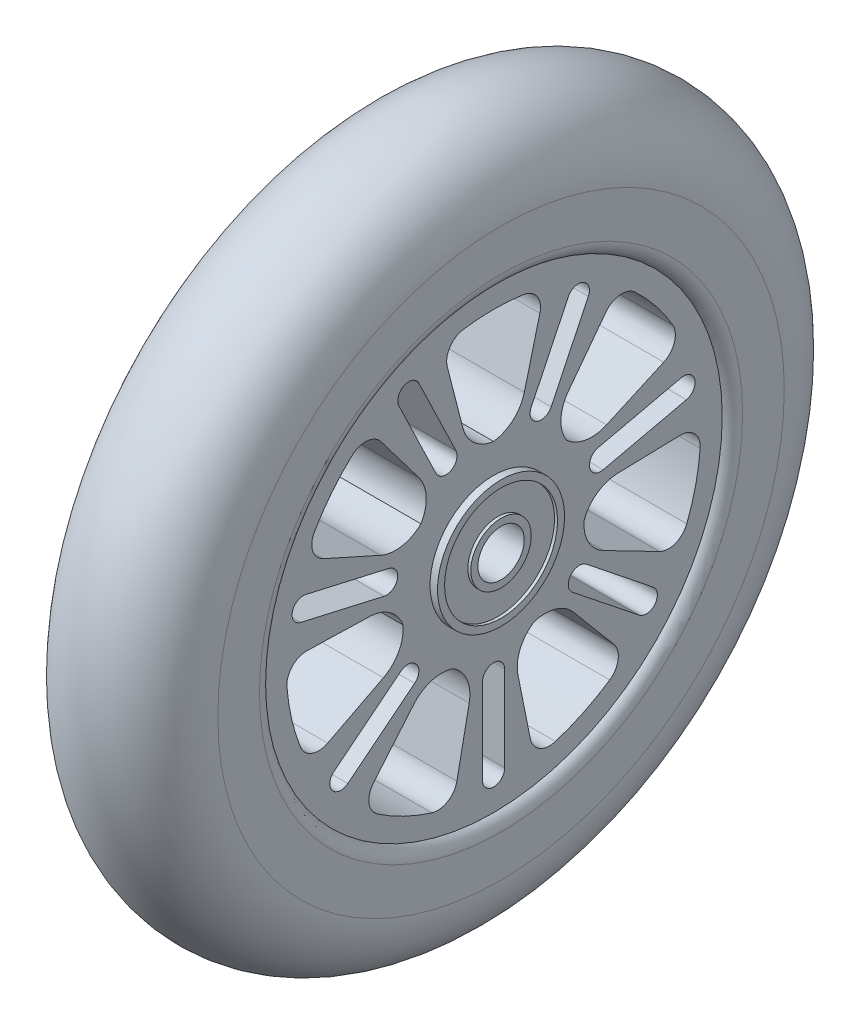
SolidWorks part; units mm, degrees
ref_plane "Front Plane" through (0, 0, 0) normal (0, 0, 1) x (1, 0, 0)
ref_plane "Top Plane" through (0, 0, 0) normal (0, 1, 0) x (1, 0, 0)
ref_plane "Right Plane" through (0, 0, 0) normal (1, 0, 0) x (0, 0, -1)
sketch "Sketch1" plane through (0, 0, 0) normal (0, 1, 0) x (1, 0, 0)
  line L0 (-12.065, 60.198) -> (-12.065, 0) construction
  line L1 (0, 0) -> (-24.13, 0)
  line L2 (0, 0) -> (0, 48.133)
  line L4 (-24.13, 0) -> (-24.13, 48.133)
  arc A0 (0, 48.133) -> (-24.13, 48.133) centre (-12.065, 48.133) ccw
  dimension "D1" = 60.198
  dimension "D2" = 24.13
revolve "Revolve1" add sketch "Sketch1" angle 360 about L1
sketch "Sketch2" plane through (0, 0, 0) normal (1, 0, 0) x (0, 0, -1)
  circle A0 centre (0, 0) radius 39.37 construction
  circle A1 centre (0, 0) radius 10.795 construction
  circle A2 centre (0, 0) radius 3.937
  dimension "D1" = 78.74
  dimension "D2" = 21.59
  dimension "D3" = 7.874
extrude "Cut-Extrude1" cut sketch "Sketch2" against normal through all
sketch "Sketch3" plane through (0, 0, 0) normal (1, 0, 0) x (0, 0, -1)
  line L0 (0.0012, -0.001) -> (-6.8326, 14.1885) construction
  line L1 (7.8687, 30.719) -> (5.2261, 20.4024)
  line L2 (-7.8687, 30.719) -> (-5.2261, 20.4024)
  line L3 (19.1114, 25.3058) -> (12.6932, 16.8074)
  line L4 (28.9235, 13.0018) -> (19.21, 8.6355)
  line L5 (31.701, 0.8368) -> (21.055, 0.5561)
  line L6 (28.1991, -14.5061) -> (18.7291, -9.634)
  line L7 (20.4198, -24.2623) -> (13.5627, -16.1139)
  line L8 (6.2409, -31.0905) -> (4.1456, -20.649)
  line L9 (-6.2371, -31.0914) -> (-4.1418, -20.6498)
  line L10 (-20.416, -24.2632) -> (-13.5589, -16.1148)
  line L11 (-28.1967, -14.508) -> (-18.7267, -9.636)
  line L12 (-31.6986, 0.8348) -> (-21.0525, 0.5541)
  line L13 (-28.9228, 13.0002) -> (-19.2092, 8.634)
  line L14 (-19.1107, 25.3042) -> (-12.6924, 16.8058)
  line L15 (-12.6962, 30.715) -> (-6.3919, 17.6251)
  line L16 (-16.0986, 29.0763) -> (-9.7944, 15.9865)
  line L17 (-17.3581, 36.043) -> (-23.3474, 48.4789) construction
  line L18 (-8.4846, 13.2669) -> (-8.4845, 13.2668)
  line L19 (16.0984, 29.0776) -> (9.7949, 15.9873)
  line L20 (12.6958, 30.716) -> (6.3924, 17.6257)
  line L21 (32.7713, 5.5441) -> (18.6068, 2.3107)
  line L22 (31.9308, 9.2259) -> (17.7663, 5.9924)
  line L23 (24.7675, -22.1641) -> (13.4081, -13.1059)
  line L24 (27.122, -19.2115) -> (15.7626, -10.1533)
  line L25 (-1.8859, -33.1824) -> (-1.8864, -18.6535)
  line L26 (1.8905, -33.1822) -> (1.89, -18.6534)
  line L27 (-27.1185, -19.2136) -> (-15.7597, -10.1546)
  line L28 (-24.7638, -22.1661) -> (-13.405, -13.1071)
  line L29 (-31.9295, 9.2234) -> (-17.7648, 5.9909)
  line L30 (-32.7697, 5.5416) -> (-18.605, 2.3091)
  circle A0 centre (0, 0) radius 40.005
  circle A1 centre (0, 0) radius 15.748
  arc A2 (5.1212, 34.8487) -> (-5.1212, 34.8487) centre (0, 0) ccw
  arc A3 (7.8687, 30.719) -> (5.1212, 34.8487) centre (4.636, 31.5471) ccw
  arc A4 (0, 15.7842) -> (5.2261, 20.4024) centre (-0.789, 21.9431) ccw
  arc A5 (0, 15.7842) -> (-5.2261, 20.4024) centre (0.789, 21.9431) cw
  arc A6 (-7.8687, 30.719) -> (-5.1212, 34.8487) centre (-4.636, 31.5471) cw
  arc A7 (19.1114, 25.3058) -> (24.0531, 25.7325) centre (21.7744, 23.2946) cw
  arc A8 (30.4392, 17.7247) -> (24.0531, 25.7325) centre (0.0004, 0.0008) ccw
  arc A9 (28.9235, 13.0018) -> (30.4392, 17.7247) centre (27.5554, 16.0455) ccw
  arc A10 (12.3409, 9.842) -> (19.21, 8.6355) centre (16.6643, 14.299) ccw
  arc A11 (12.3409, 9.842) -> (12.6932, 16.8074) centre (17.6482, 13.0652) cw
  arc A12 (31.701, 0.8368) -> (35.1157, -2.7608) centre (31.789, -2.4991) cw
  arc A13 (32.8366, -12.7464) -> (35.1157, -2.7608) centre (0.0012, 0.001) ccw
  arc A14 (28.1991, -14.5061) -> (32.8366, -12.7464) centre (29.7257, -11.5387) ccw
  arc A15 (15.3896, -3.5113) -> (18.7291, -9.634) centre (21.5698, -4.1126) ccw
  arc A16 (15.3896, -3.5113) -> (21.055, 0.5561) centre (21.2186, -5.6511) cw
  arc A17 (20.4198, -24.2623) -> (19.7362, -29.1751) centre (17.8666, -26.411) cw
  arc A18 (10.5081, -33.6191) -> (19.7362, -29.1751) centre (0.0019, 0.0004) ccw
  arc A19 (6.2409, -31.0905) -> (10.5081, -33.6191) centre (9.5128, -30.434) ccw
  arc A20 (6.8504, -14.2206) -> (4.1456, -20.649) centre (10.2336, -19.4273) ccw
  arc A21 (6.8504, -14.2206) -> (13.5627, -16.1139) centre (8.8118, -20.112) cw
  arc A22 (-6.2371, -31.0914) -> (-10.5043, -33.62) centre (-9.509, -30.4349) cw
  arc A23 (-19.7324, -29.176) -> (-10.5043, -33.62) centre (0.0019, -0.0004) ccw
  arc A24 (-20.416, -24.2632) -> (-19.7324, -29.176) centre (-17.8628, -26.4119) ccw
  arc A25 (-6.8466, -14.2215) -> (-13.5589, -16.1148) centre (-8.808, -20.1129) ccw
  arc A26 (-6.8466, -14.2215) -> (-4.1418, -20.6498) centre (-10.2298, -19.4282) cw
  arc A27 (-28.1967, -14.508) -> (-32.8341, -12.7483) centre (-29.7233, -11.5406) cw
  arc A28 (-35.1133, -2.7627) -> (-32.8341, -12.7483) centre (0.0012, -0.001) ccw
  arc A29 (-31.6986, 0.8348) -> (-35.1133, -2.7627) centre (-31.7865, -2.5011) ccw
  arc A30 (-15.3872, -3.5133) -> (-21.0525, 0.5541) centre (-21.2162, -5.653) ccw
  arc A31 (-15.3872, -3.5133) -> (-18.7267, -9.636) centre (-21.5673, -4.1145) cw
  arc A32 (-28.9228, 13.0002) -> (-30.4384, 17.7231) centre (-27.5546, 16.0439) cw
  arc A33 (-24.0524, 25.7309) -> (-30.4384, 17.7231) centre (0.0004, -0.0008) ccw
  arc A34 (-19.1107, 25.3042) -> (-24.0524, 25.7309) centre (-21.7736, 23.2931) ccw
  arc A35 (-12.3402, 9.8405) -> (-12.6924, 16.8058) centre (-17.6474, 13.0636) ccw
  arc A36 (-12.3402, 9.8405) -> (-19.2092, 8.634) centre (-16.6635, 14.2974) cw
  arc A37 (-12.6962, 30.715) -> (-16.0986, 29.0763) centre (-14.3974, 29.8957) ccw
  arc A38 (-9.7944, 15.9865) -> (-6.3919, 17.6251) centre (-8.0932, 16.8058) ccw
  arc A39 (16.0984, 29.0776) -> (12.6958, 30.716) centre (14.3971, 29.8968) ccw
  arc A40 (6.3924, 17.6257) -> (9.7949, 15.9873) centre (8.0937, 16.8065) ccw
  arc A41 (32.7713, 5.5441) -> (31.9308, 9.2259) centre (32.3511, 7.385) ccw
  arc A42 (17.7663, 5.9924) -> (18.6068, 2.3107) centre (18.1866, 4.1516) ccw
  arc A43 (24.7675, -22.1641) -> (27.122, -19.2115) centre (25.9448, -20.6878) ccw
  arc A44 (15.7626, -10.1533) -> (13.4081, -13.1059) centre (14.5853, -11.6296) ccw
  arc A45 (-1.8859, -33.1824) -> (1.8905, -33.1822) centre (0.0023, -33.1823) ccw
  arc A46 (1.89, -18.6534) -> (-1.8864, -18.6535) centre (0.0018, -18.6534) ccw
  arc A47 (-27.1185, -19.2136) -> (-24.7638, -22.1661) centre (-25.9412, -20.6898) ccw
  arc A48 (-13.405, -13.1071) -> (-15.7597, -10.1546) centre (-14.5823, -11.6309) ccw
  arc A49 (-31.9295, 9.2234) -> (-32.7697, 5.5416) centre (-32.3496, 7.3825) ccw
  arc A50 (-18.605, 2.3091) -> (-17.7648, 5.9909) centre (-18.1849, 4.15) ccw
  dimension "D1" = 80.01
  dimension "D2" = 31.496
  dimension "D4" = 11.345
  dimension "D3" = 7
  dimension "D5" = 7
extrude "Cut-Extrude2" cut sketch "Sketch3" against normal through all contours A6 L2 A5 A4 L1 A3 A2 | L16 A38 L15 A37 | A36 A35 L14 A34 A33 A32 L13 | L30 A50 L29 A49 | A31 A30 L12 A29 A28 A27 L11 | L28 A48 L27 A47 | A26 A25 L10 A24 A23 A22 L9 | L26 A46 L25 A45 | A21 A20 L8 A19 A18 A17 L7 | L24 A44 L23 A43 | A16 A15 L6 A14 A13 A12 L5 | L22 A42 L21 A41 | A11 A10 L4 A9 A8 A7 L3 | L20 A40 L19 A39 region at (0, 26.7042, 0) region at (0, 16.6506, -20.8785) region at (0, -5.9413, -26.0359) region at (0, -24.0592, -11.5884) region at (0, -24.0601, 11.5846) region at (0, -5.9432, 26.0334) region at (0, 16.649, 20.8778) region at (0, 23.3507, 11.2453) region at (0, 23.3516, -11.2454) region at (0, 5.7683, -25.2688) region at (0, -16.1587, -20.2651) region at (0, -25.9179, -0.0021) region at (0, -16.1603, 20.2617) region at (0, 5.7662, 25.2673)
sketch "Sketch5" plane through (0, 0, 0) normal (1, 0, 0) x (0, 0, -1)
  circle A0 centre (0, 0) radius 38.858
  circle A1 centre (0, 0) radius 10.795
extrude "Cut-Extrude3" cut sketch "Sketch5" against normal blind 1.27
ref_plane "Plane1" through (-12.065, 0, 0) normal (1, 0, 0) x (0, 0, -1)
sketch "Sketch6" plane through (-24.13, 0, 0) normal (-1, 0, 0) x (0, 0, 1)
  circle A0 centre (0, 0) radius 9.5986
  circle A1 centre (0, 0) radius 5.1361
extrude "Cut-Extrude4" cut sketch "Sketch6" against normal blind 0.508
mirror "Mirror8" about plane through (-12.065, 0, 0) normal (1, 0, 0) of "Cut-Extrude3"
mirror "Mirror11" about plane through (-12.065, 0, 0) normal (1, 0, 0) of "Cut-Extrude4"
fillet "Fillet3" radius 2.54 2 edges at (-24.13, 0, -38.858) (0, 0, -38.858)
